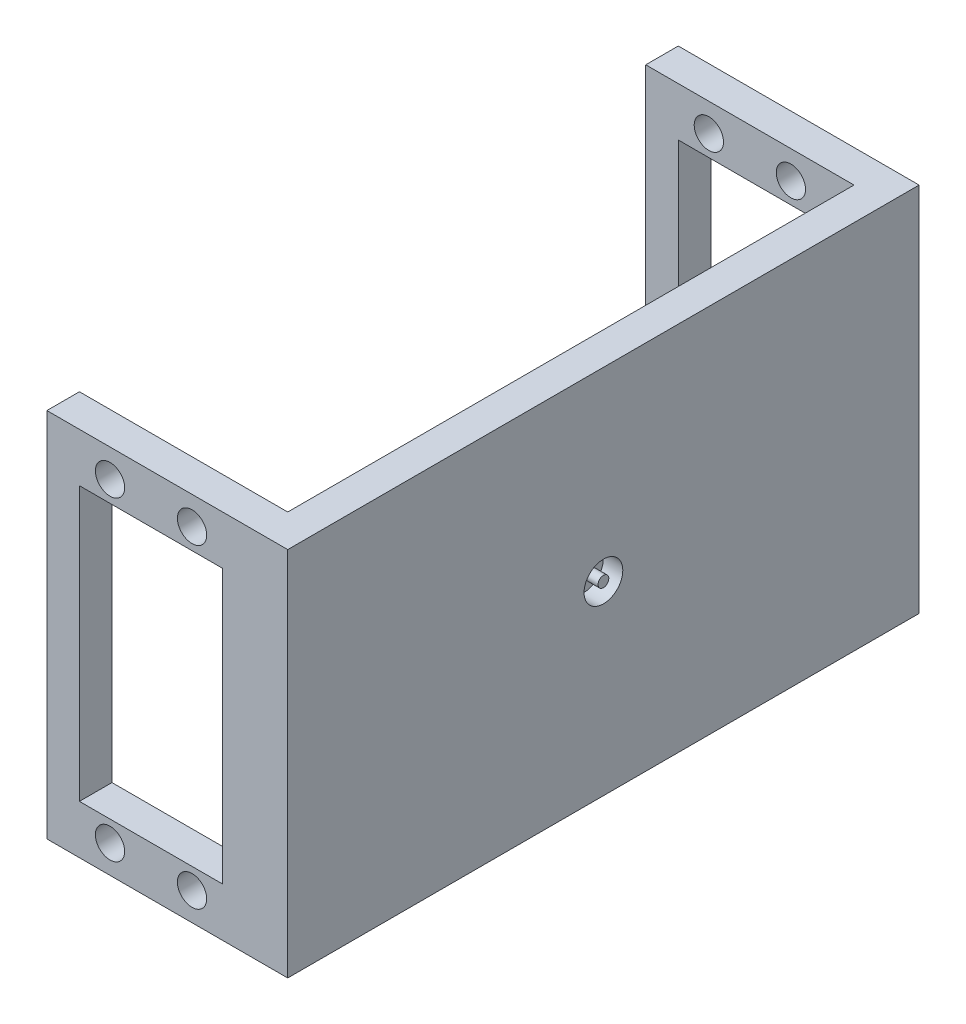
SolidWorks part; units mm, degrees
ref_plane "Front Plane" through (0, 0, 0) normal (0, 0, 1) x (1, 0, 0)
ref_plane "Top Plane" through (0, 0, 0) normal (0, 1, 0) x (1, 0, 0)
ref_plane "Right Plane" through (0, 0, 0) normal (1, 0, 0) x (0, 0, -1)
sketch "Sketch1" plane through (0, 0, 0) normal (0, 0, 1) x (1, 0, 0)
  line L9 (-11, 0) -> (11, 0)
  line L10 (-11, 0) -> (-11, 42)
  line L11 (-11, 42) -> (11, 42)
  line L12 (11, 0) -> (11, 42)
  line L17 (-16, -7.5) -> (16, -7.5)
  line L18 (-16, -7.5) -> (-16, 49.5)
  line L19 (-16, 49.5) -> (16, 49.5)
  line L20 (16, -7.5) -> (16, 49.5)
  point P4 (0, 0)
  dimension "D1" = 22
  dimension "D2" = 42
  dimension "D4" = 5
  dimension "D5" = 7.5
  dimension "D3" = 5
  dimension "D6" = 7.5
extrude "Servo Mount" add sketch "Sketch1" along normal blind 5
hole_wizard "Servo Mount Holes" positions "Sketch2" profile "Sketch3" hole size "M4" standard "ANSI Metric" end condition through all
sketch "Sketch2" plane through (0, 0, 5) normal (0, 0, 1) x (1, 0, 0)
  line L1 (-6.3, 45.2) -> (6.3, 45.2) construction
  line L2 (-6.3, 45.2) -> (-6.3, -3.2) construction
  line L3 (-6.3, -3.2) -> (6.3, -3.2) construction
  line L4 (6.3, 45.2) -> (6.3, -3.2) construction
  line L5 (-16, 49.5) -> (-16, -7.5) construction
  line L7 (-16, 21) -> (16, 21) construction
  line L8 (16, -7.5) -> (16, 49.5) construction
  line L10 (0, 49.5) -> (0, -7.5) construction
  line L11 (16, 49.5) -> (-16, 49.5) construction
  line L12 (-16, -7.5) -> (16, -7.5) construction
  point P0 (-6.3, 45.2)
  point P2 (-6.3, -3.2)
  point P4 (6.3, 45.2)
  point P6 (6.3, -3.2)
  point P96 (-6.3, 21)
  point P97 (0, -3.2)
  dimension "D1" = 48.4
  dimension "D2" = 12.6
sketch "Sketch3" plane through (-6.3, 45.2, 5) normal (1, 0, 0) x (0, -1, 0)
  line L0 (0, 0) -> (0, 5)
  line L1 (0, 5) -> (2.25, 5)
  line L2 (2.25, 5) -> (2.25, 0)
  line L5 (2.25, 0) -> (0, 0)
  line L11 (0, -6.35) -> (0, 107.95) construction
  dimension "Thru Hole Dia." = 4.5
  dimension "Thru Hole Depth" = 5
sketch "Sketch4" plane through (16, 0, 0) normal (1, 0, 0) x (0, 0, -1)
  line L0 (-5, -7.5) -> (0, -7.5) construction
  line L1 (0, -7.5) -> (-97, -7.5)
  line L2 (0, -7.5) -> (0, 49.5)
  line L3 (0, 49.5) -> (-97, 49.5)
  line L4 (-97, -7.5) -> (-97, 49.5)
  line L5 (-5, 49.5) -> (0, 49.5) construction
  line L8 (0, -7.5) -> (0, 49.5) construction
  circle A0 centre (-48.5, 21) radius 2.975
  circle A1 centre (-48.5, 21) radius 0.825
  circle A3 centre (-48.5, 21) radius 3.975
  point P10 (0, 21)
  dimension "D1" = 1.65
  dimension "D2" = 5.95
  dimension "D4" = 97
  dimension "D5" = 48.5
extrude "Axle Mount Base" add sketch "Sketch4" along normal blind 5 contours L3 L4 L1 L2
extrude "Axle Mount" cut sketch "Sketch4<4>" against normal blind 3 from surface contours A0 A1 region at (16, 21, 51.3909) starting at face at (21, 21, 48.5)
sketch "Sketch4<4>" plane through (16, 0, 0) normal (1, 0, 0) x (0, 0, -1) same geometry as "Sketch4"
ref_plane "Plane1" through (0, 0, 48.5) normal (0, 0, -1) x (-1, 0, 0)
mirror "Mirror1" about plane through (0, 0, 48.5) normal (0, 0, -1) of "Servo Mount Holes", "Servo Mount"
equation "\"D3@Sketch1\"=\"D4@Sketch1\""
equation "\"D6@Sketch1\"=\"D5@Sketch1\""
equation "\"D1@Sketch4\"=1.85 - 0.2"
equation "\"D2@Sketch4\"=5.75+0.2"
equation "\"D4@Sketch4\"=2*\"D5@Sketch4\""
